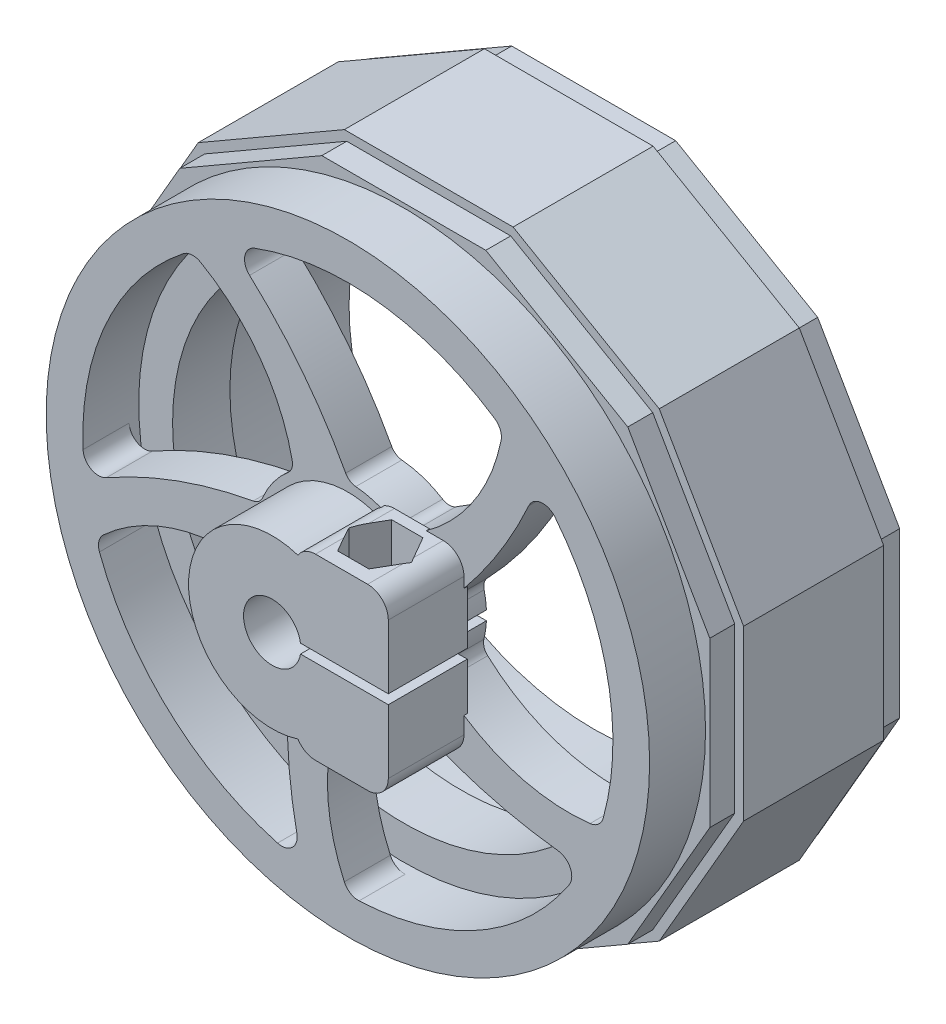
SolidWorks part; units mm, degrees
ref_plane "Front Plane" through (0, 0, 0) normal (0, 0, 1) x (1, 0, 0)
ref_plane "Top Plane" through (0, 0, 0) normal (0, 1, 0) x (1, 0, 0)
ref_plane "Right Plane" through (0, 0, 0) normal (1, 0, 0) x (0, 0, -1)
sketch "S01 - Smaller twelve-flat end bead seats" plane through (0, 0, 0) normal (0, 0, 1) x (1, 0, 0)
  line L0 (32.5517, 8.7222) -> (23.8295, 23.8295)
  line L1 (23.8295, 23.8295) -> (8.7222, 32.5517)
  line L2 (8.7222, 32.5517) -> (-8.7222, 32.5517)
  line L3 (-8.7222, 32.5517) -> (-23.8295, 23.8295)
  line L4 (-23.8295, 23.8295) -> (-32.5517, 8.7222)
  line L5 (-32.5517, 8.7222) -> (-32.5517, -8.7222)
  line L6 (-32.5517, -8.7222) -> (-23.8295, -23.8295)
  line L7 (-23.8295, -23.8295) -> (-8.7222, -32.5517)
  line L8 (-8.7222, -32.5517) -> (8.7222, -32.5517)
  line L9 (8.7222, -32.5517) -> (23.8295, -23.8295)
  line L10 (23.8295, -23.8295) -> (32.5517, -8.7222)
  line L11 (32.5517, -8.7222) -> (32.5517, 8.7222)
  circle A0 centre (0, 0) radius 24.6
  dimension "D1" = 49.2
  dimension "D2" = 8.7222
  dimension "D3" = 23.8295
  dimension "D4" = 32.5517
  dimension "D5" = 8.7222
  dimension "D6" = 23.8295
  dimension "D7" = 32.5517
  dimension "D8" = 8.7222
  dimension "D9" = 23.8295
  dimension "D10" = 32.5517
  dimension "D11" = 8.7222
  dimension "D12" = 23.8295
  dimension "D13" = 32.5517
extrude "01 - Smaller twelve-flat end bead seats" add sketch "S01 - Smaller twelve-flat end bead seats" along normal blind 20.2
sketch "S02 - Raised central tyre drive key" plane through (0, 0, 0) normal (0, 0, 1) x (1, 0, 0)
  line L0 (33.4983, 8.9758) -> (24.5225, 24.5225)
  line L1 (24.5225, 24.5225) -> (8.9758, 33.4983)
  line L2 (8.9758, 33.4983) -> (-8.9758, 33.4983)
  line L3 (-8.9758, 33.4983) -> (-24.5225, 24.5225)
  line L4 (-24.5225, 24.5225) -> (-33.4983, 8.9758)
  line L5 (-33.4983, 8.9758) -> (-33.4983, -8.9758)
  line L6 (-33.4983, -8.9758) -> (-24.5225, -24.5225)
  line L7 (-24.5225, -24.5225) -> (-8.9758, -33.4983)
  line L8 (-8.9758, -33.4983) -> (8.9758, -33.4983)
  line L9 (8.9758, -33.4983) -> (24.5225, -24.5225)
  line L10 (24.5225, -24.5225) -> (33.4983, -8.9758)
  line L11 (33.4983, -8.9758) -> (33.4983, 8.9758)
  circle A0 centre (0, 0) radius 24.6
  dimension "D1" = 49.2
  dimension "D2" = 8.9758
  dimension "D3" = 24.5225
  dimension "D4" = 33.4983
  dimension "D5" = 8.9758
  dimension "D6" = 24.5225
  dimension "D7" = 33.4983
  dimension "D8" = 8.9758
  dimension "D9" = 24.5225
  dimension "D10" = 33.4983
  dimension "D11" = 8.9758
  dimension "D12" = 24.5225
  dimension "D13" = 33.4983
extrude "02 - Raised central tyre drive key" add sketch "S02 - Raised central tyre drive key" along normal blind 14.9 from offset 2.65
sketch "S03 - Inboard 6808 outer race seat" plane through (0, 0, 0) normal (0, 0, 1) x (1, 0, 0)
  circle A0 centre (0, 0) radius 26.1
  dimension "D1" = 52.2
extrude "03 - Inboard 6808 outer race seat" [suppressed] cut sketch "S03 - Inboard 6808 outer race seat" along normal blind 7.2 from offset 0.1 offset against normal yes
sketch "S04 - Outboard 6808 outer race seat" plane through (0, 0, 0) normal (0, 0, 1) x (1, 0, 0)
  circle A0 centre (0, 0) radius 26.1
  dimension "D1" = 52.2
extrude "04 - Outboard 6808 outer race seat" [suppressed] cut sketch "S04 - Outboard 6808 outer race seat" along normal blind 7.2 from offset 13.1
sketch "S05 - Three tyre-flange through holes" plane through (0, 0, 0) normal (0, 0, 1) x (1, 0, 0)
  circle A0 centre (28.8329, 7.7257) radius 1.7
  circle A1 centre (-21.1071, 21.1071) radius 1.7
  circle A2 centre (-7.7257, -28.8329) radius 1.7
  dimension "D1" = 3.4
  dimension "D2" = 3.4
  dimension "D3" = 3.4
  dimension "D4" = 28.8329
  dimension "D5" = 7.7257
  dimension "D6" = 21.1071
  dimension "D7" = 7.7257
  dimension "D8" = 21.1071
  dimension "D9" = 28.8329
extrude "05 - Three tyre-flange through holes" [suppressed] cut sketch "S05 - Three tyre-flange through holes" along normal blind 20.4 from offset 0.1 offset against normal yes
sketch "Pair of 6808 bearing seats layout" plane through (0, 0, 0) normal (0, 0, 1) x (1, 0, 0)
  circle A0 centre (0, 0) radius 26.025
extrude "Pair of 6808 bearing seats" cut sketch "Pair of 6808 bearing seats layout" against normal blind 14.22 from offset 14.1
sketch "Rim crown for spoke tips layout" plane through (0, 0, 0) normal (0, 0, 1) x (1, 0, 0)
  circle A0 centre (0, 0) radius 32.1
  circle A1 centre (0, 0) radius 28.2
extrude "Rim crown for spoke tips" add sketch "Rim crown for spoke tips layout" along normal blind 6.25 from offset 19.9
sketch "Five swept load-bearing spokes layout" plane through (0, 0, 0) normal (0, 0, 1) x (1, 0, 0)
  line L0 (16.7079, 26.0956) -> (21.2784, 22.5247)
  line L1 (7.9337, 1.4997) -> (3.878, 7.0819)
  line L2 (-19.6553, 23.9541) -> (-14.8469, 27.1975)
  line L3 (1.0253, 8.0088) -> (-5.537, 5.8766)
  line L4 (-28.8556, -11.2911) -> (-30.4543, -5.7158)
  line L5 (-7.3, 3.45) -> (-7.3, -3.45)
  line L6 (1.8216, -30.9324) -> (-3.9749, -30.73)
  line L7 (-5.537, -5.8766) -> (1.0253, -8.0088)
  line L8 (29.9814, -7.8262) -> (27.9977, -13.2764)
  line L9 (3.878, -7.0819) -> (7.9337, -1.4997)
  arc A0 (3.878, 7.0819) -> (16.7079, 26.0956) centre (-3.3909, 25.8223) ccw
  arc A1 (21.2784, 22.5247) -> (7.9337, 1.4997) centre (-25.7766, 37.6433) cw
  arc A2 (-5.537, 5.8766) -> (-19.6553, 23.9541) centre (-25.6063, 4.7546) ccw
  arc A3 (-14.8469, 27.1975) -> (1.0253, 8.0088) centre (-43.7663, -12.8826) cw
  arc A4 (-7.3, -3.45) -> (-28.8556, -11.2911) centre (-12.4347, -22.8838) ccw
  arc A5 (-30.4543, -5.7158) -> (-7.3, 3.45) centre (-1.2725, -45.6052) cw
  arc A6 (1.0253, -8.0088) -> (1.8216, -30.9324) centre (17.9213, -18.8976) ccw
  arc A7 (-3.9749, -30.73) -> (-5.537, -5.8766) centre (42.9799, -15.303) cw
  arc A8 (7.9337, -1.4997) -> (29.9814, -7.8262) centre (23.5106, 11.2045) ccw
  arc A9 (27.9977, -13.2764) -> (3.878, -7.0819) centre (27.8355, 36.1474) cw
extrude "Five swept load-bearing spokes" add sketch "Five swept load-bearing spokes layout" along normal blind 4.9 from offset 21.25
sketch "Spoke root hub layout" plane through (0, 0, 0) normal (0, 0, 1) x (1, 0, 0)
  circle A0 centre (0, 0) radius 9.85
extrude "Spoke root hub" add sketch "Spoke root hub layout" along normal blind 4.9 from offset 21.25
fillet "Blended spoke tips to rim" radius 1.65 10 edges at (20.2474, 19.6286, 23.7) (16.4924, 22.8744, 23.7) (24.9247, -13.1909, 23.7) (26.8513, -8.6167, 23.7) (-4.8431, -27.781, 23.7) (0.1026, -28.1998, 23.7) (-27.9179, -3.9787, 23.7) (-26.7879, -8.8118, 23.7) (-12.4111, 25.322, 23.7) (-16.6584, 22.7538, 23.7)
fillet "Blended spoke roots to hub" radius 1.35 10 edges at (-5.767, 7.9853, 23.7) (-9.3301, 3.1577, 23.7) (-9.3765, -3.0171, 23.7) (-5.8863, -7.8977, 23.7) (-0.0281, -9.85, 23.7) (5.6922, -8.0387, 23.7) (9.3592, -3.0705, 23.7) (9.4043, 2.9295, 23.7) (5.8124, 7.9523, 23.7) (0.12, 9.8493, 23.7)
sketch "Motor shaft clamp barrel layout" plane through (0, 0, 0) normal (0, 0, 1) x (1, 0, 0)
  circle A0 centre (0, 0) radius 8.9
extrude "Motor shaft clamp barrel" add sketch "Motor shaft clamp barrel layout" along normal blind 8.4 from offset 25.8
sketch "Rounded clamp jaws layout" plane through (0, 0, 0) normal (0, 0, 1) x (1, 0, 0)
  line L0 (4.6, -9.5) -> (10.15, -9.5)
  line L1 (12.35, -7.3) -> (12.35, 7.3)
  line L2 (10.15, 9.5) -> (4.6, 9.5)
  line L3 (2.4, 7.3) -> (2.4, -7.3)
  arc A0 (10.15, -9.5) -> (12.35, -7.3) centre (10.15, -7.3) ccw
  arc A1 (12.35, 7.3) -> (10.15, 9.5) centre (10.15, 7.3) ccw
  arc A2 (4.6, 9.5) -> (2.4, 7.3) centre (4.6, 7.3) ccw
  arc A3 (2.4, -7.3) -> (4.6, -9.5) centre (4.6, -7.3) ccw
extrude "Rounded clamp jaws" add sketch "Rounded clamp jaws layout" along normal blind 8.4 from offset 25.8
sketch "Johnson shaft - 6.10 mm bore layout" plane through (0, 0, 0) normal (0, 0, 1) x (1, 0, 0)
  circle A0 centre (0, 0) radius 3.05
extrude "Johnson shaft - 6.10 mm bore" cut sketch "Johnson shaft - 6.10 mm bore layout" against normal blind 13.2 from offset 34.35
sketch "Clamp split layout" plane through (0, 0, 0) normal (0, 0, 1) x (1, 0, 0)
  line L0 (0, -0.5) -> (13.5, -0.5)
  line L1 (13.5, -0.5) -> (13.5, 0.5)
  line L2 (13.5, 0.5) -> (0, 0.5)
  line L3 (0, 0.5) -> (0, -0.5)
extrude "Open pinch slot" cut sketch "Clamp split layout" against normal blind 13.16 from offset 34.32
sketch "M3 pinch bolt clearance layout" plane through (0, 0, 0) normal (0, 1, 0) x (1, 0, 0)
  circle A0 centre (7.15, -29.85) radius 1.65
extrude "M3 pinch bolt clearance" cut sketch "M3 pinch bolt clearance layout" against normal blind 28 from offset 14
sketch "M3 screw head seat layout" plane through (0, 0, 0) normal (0, 1, 0) x (1, 0, 0)
  circle A0 centre (7.15, -29.85) radius 3
extrude "M3 screw head seat" cut sketch "M3 screw head seat layout" against normal blind 6.5 from offset 7.5 offset against normal yes
sketch "Captured M3 nut seat layout" plane through (0, 0, 0) normal (0, 1, 0) x (1, 0, 0)
  line L0 (10.4698, -29.85) -> (8.8099, -32.725)
  line L1 (8.8099, -32.725) -> (5.4901, -32.725)
  line L2 (5.4901, -32.725) -> (3.8302, -29.85)
  line L3 (3.8302, -29.85) -> (5.4901, -26.975)
  line L4 (5.4901, -26.975) -> (8.8099, -26.975)
  line L5 (8.8099, -26.975) -> (10.4698, -29.85)
extrude "Captured M3 nut seat" cut sketch "Captured M3 nut seat layout" against normal blind 9 from offset 14
